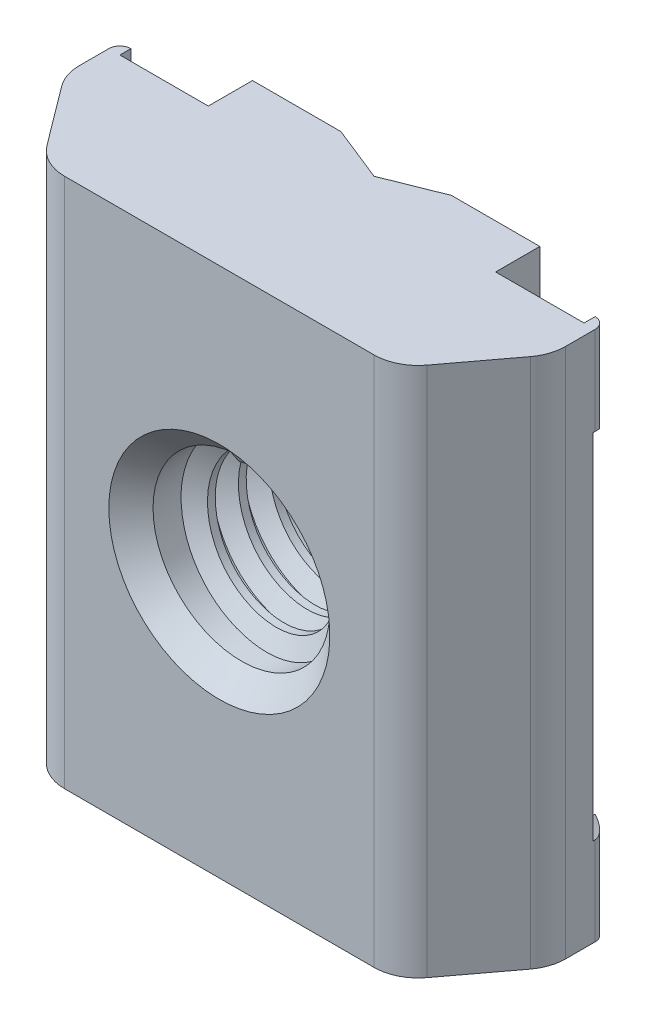
SolidWorks part; units mm, degrees
material "AISI Type A2 Tool Steel"
ref_plane "Front Plane" through (0, 0, 0) normal (0, 0, 1) x (1, 0, 0)
ref_plane "Top Plane" through (0, 0, 0) normal (0, 1, 0) x (1, 0, 0)
ref_plane "Right Plane" through (0, 0, 0) normal (1, 0, 0) x (0, 0, -1)
sketch "Sketch2" plane through (0, 0, 0) normal (0, 1, 0) x (1, 0, 0)
  line L0 (0, 0) -> (8, 0)
  line L1 (8, 0) -> (9.5, 2)
  line L2 (9.5, 2) -> (9.5, 3.25)
  line L6 (7.25, 3) -> (7.25, 4)
  line L7 (7.25, 4) -> (5.25, 4)
  line L10 (2.75, 4) -> (0.75, 4)
  line L11 (0.75, 4) -> (0.75, 3)
  line L12 (0.75, 3) -> (-1.25, 3)
  line L13 (-1.25, 3) -> (-1.25, 3.25)
  line L14 (-1.25, 3.25) -> (-1.5, 3.25)
  line L15 (-1.5, 3.25) -> (-1.5, 2)
  line L16 (-1.5, 2) -> (0, 0)
  line L17 (9.5, 3.25) -> (9.25, 3.25)
  line L18 (9.25, 3.25) -> (9.25, 3)
  line L19 (9.25, 3) -> (7.25, 3)
  line L20 (-1.5, 2) -> (9.5, 2) construction
  line L21 (2.75, 4) -> (4, 3.5)
  line L22 (4, 3.5) -> (5.25, 4)
  point P4 (4, 2)
  point P22 (4, 0)
  dimension "D1" = 8
  dimension "D2" = 11
  dimension "D3" = 2
  dimension "D4" = 1
  dimension "D5" = 2
  dimension "D6" = 0.25
  dimension "D7" = 1
  dimension "D8" = 2
  dimension "D9" = 2
  dimension "D10" = 0.5
  dimension "D11" = 0.25
extrude "Boss-Extrude1" add sketch "Sketch2" along normal blind 12
fillet "Fillet1" radius 1 4 edges at (-1.5, 6, -2) (9.5, 6, -2) (8, 6, 0) (0, 6, 0)
sketch "Sketch4" plane through (0, 0, -4) normal (0, 0, -1) x (-1, 0, 0)
  line L0 (-4, 12) -> (-4, 0) construction
  circle A0 centre (-4, 6) radius 2
  dimension "D1" = 4
extrude "Cut-Extrude1" cut sketch "Sketch4" against normal through all
thread "Thread1" pitch 0.7 start angle 0, offset 0.5, length 0, pitch 0.7, diameter 4
ref_plane "Plane1" through (6, 6, -3.5) normal (0, -1, 0) x (1, 0, 0)
sketch "Thread Profile1" plane through (6, 6, -3.5) normal (0, -1, 0) x (1, 0, 0)
  line L0 (0, 0) -> (0, 0.7) construction
  line L11 (0, 0) -> (0, 0.6125)
  line L12 (0, 0.6125) -> (-0.3789, 0.3937)
  line L13 (-0.3789, 0.3937) -> (-0.3789, 0.2187)
  line L15 (-0.3789, 0.2187) -> (0, 0)
  line L17 (-0.3789, 0.3062) -> (0, 0.3062) construction
  point P2 (0, 0)
  dimension "Pitch" = 0.7
  dimension "Profile_Angle" = 60
  dimension "Profile_Land" = 0.175
  dimension "Profile_Height" = 0.3789
chamfer "Chamfer2" distance 0.5 angle 45 2 edges at (6, 6, -4) (2, 6, -4)
chamfer "Chamfer4" distance 0.5 angle 45 1 edges at (2, 6, 0)
sketch "Sketch8" plane through (0, 0, -3.25) normal (0, 0, -1) x (-1, 0, 0)
  line L0 (1.5, 12) -> (1.5, 0) construction
  line L3 (-9.5, 12) -> (-9.5, 0) construction
  line L4 (-9.5, 10) -> (-9.5, 2)
  line L5 (1.5, 10) -> (1.5, 2)
  arc A0 (1.5, 10) -> (1.5, 2) centre (5.2749, 6) ccw
  arc A1 (-9.5, 10) -> (-9.5, 2) centre (-13.2749, 6) cw
  dimension "D3" = 5.5
  dimension "D4" = 5.5
  dimension "D1" = 2
  dimension "D2" = 2
extrude "Cut-Extrude2" cut sketch "Sketch8" against normal blind 0.3
fillet "Fillet4" radius 0.25 4 edges at (-1.5, 11, -3.25) (-1.5, 1, -3.25) (9.5, 11, -3.25) (9.5, 1, -3.25)
